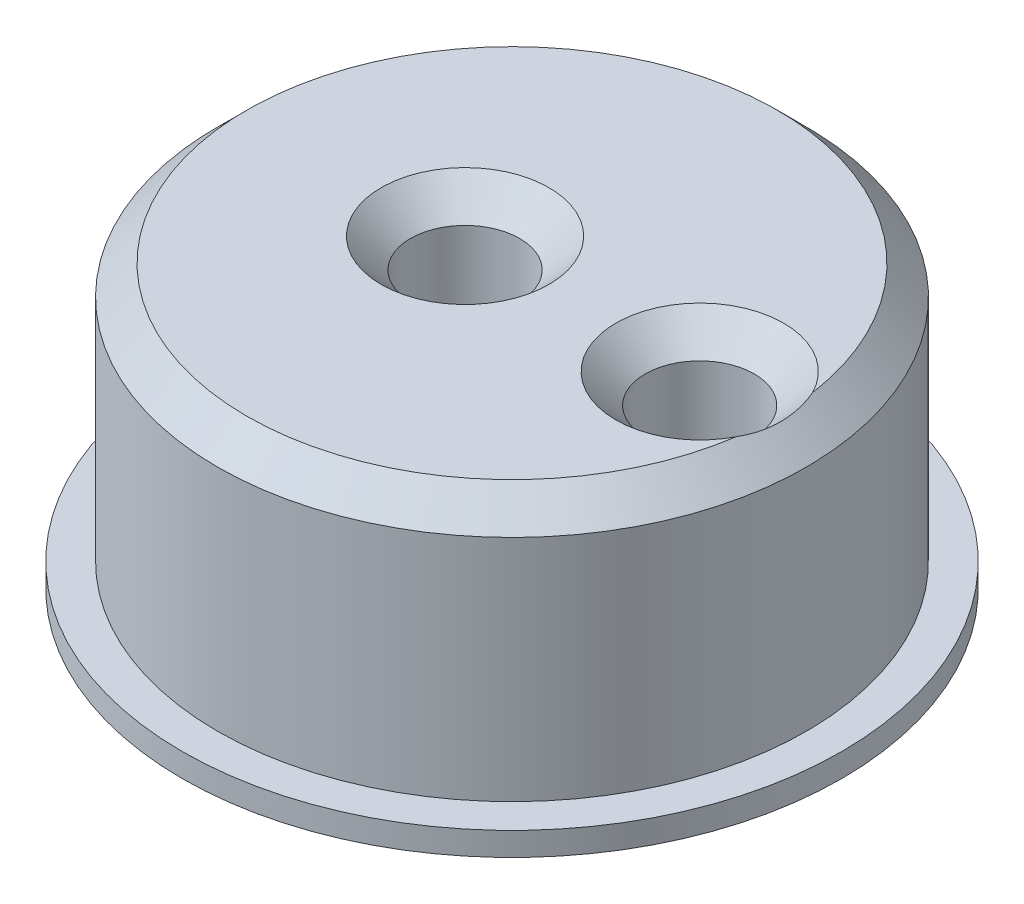
SolidWorks part; units mm, degrees
ref_plane "前视基准面" through (0, 0, 0) normal (0, 0, 1) x (1, 0, 0)
ref_plane "上视基准面" through (0, 0, 0) normal (0, 1, 0) x (1, 0, 0)
ref_plane "右视基准面" through (0, 0, 0) normal (1, 0, 0) x (0, 0, -1)
other "Configuration Table"
sketch "草图1" plane through (0, 0, 0) normal (0, 1, 0) x (1, 0, 0)
  line L0 (1.2, 6.4178) -> (1.2, -6.4114) construction
  line L1 (-5.7349, 0) -> (5.8104, 0) construction
  circle A0 centre (0, 0) radius 5.02
  circle A1 centre (3.2, 0) radius 0.93
  circle A2 centre (-0.8, 0) radius 0.93
  dimension "D1" = 10.04
  dimension "D3" = 4
  dimension "D4" = 1.86
  dimension "D2" = 1.2
extrude "凸台-拉伸1" add sketch "草图1" along normal blind 4.4
sketch "草图3" plane through (0, 0, 0) normal (0, -1, 0) x (1, 0, 0)
  circle A0 centre (3.2, 0) radius 0.93 construction
  circle A1 centre (0, 0) radius 5.02 construction
  circle A3 centre (-0.8, 0) radius 0.93 construction
  circle A4 centre (3.2, 0) radius 0.93
  circle A5 centre (-0.8, 0) radius 0.93
  circle A6 centre (0, 0) radius 5.02 construction
  circle A7 centre (0, 0) radius 5.62
  dimension "D1" = 0.6
extrude "凸台-拉伸2" add sketch "草图3" along normal blind 0.4
chamfer "倒角1" distance 0.5 angle 45 5 edges at (0, 4.4, 5.02) (-0.8, 4.4, -0.93) (3.2, 4.4, 0.93) (-0.8, -0.4, -0.93) (3.2, -0.4, -0.93)
ref_axis "基准轴1" through (0, 3.9, 0) along (0, -1, 0)
sketch "草图2" plane through (0, 0, 0) normal (0, 1, 0) x (1, 0, 0)
  line L0 (-5.9042, 0) -> (6.2358, 0) construction
